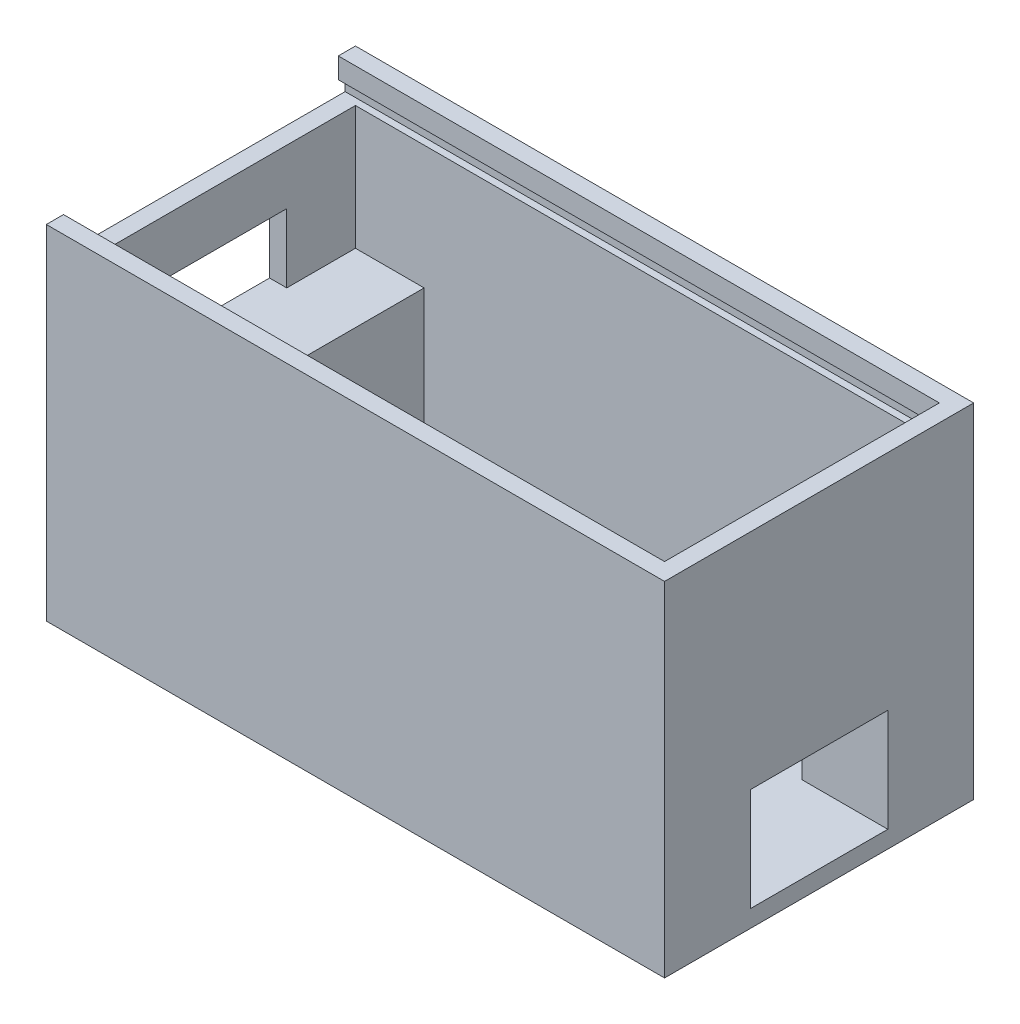
SolidWorks part; units mm, degrees
ref_plane "Front Plane" through (0, 0, 0) normal (0, 0, 1) x (1, 0, 0)
ref_plane "Top Plane" through (0, 0, 0) normal (0, 1, 0) x (1, 0, 0)
ref_plane "Right Plane" through (0, 0, 0) normal (1, 0, 0) x (0, 0, -1)
sketch "Sketch1" plane through (0, 0, 0) normal (0, 1, 0) x (1, 0, 0)
  line L1 (-40.1376, 25.9551) -> (49.8624, 25.9551)
  line L2 (-40.1376, 25.9551) -> (-40.1376, -19.0449)
  line L3 (-40.1376, -19.0449) -> (49.8624, -19.0449)
  line L4 (49.8624, 25.9551) -> (49.8624, -19.0449)
extrude "Boss-Extrude1" add sketch "Sketch1" along normal blind 50
shell "Shell1" thickness 2.5 removed face at (4.8624, 50, -3.4551)
sketch "Sketch2" plane through (-37.6376, 0, 0) normal (1, 0, 0) x (0, 0, -1)
  line L0 (-16.5449, 50) -> (-16.5449, 2.5) construction
  line L1 (23.4551, 2.5) -> (-16.5449, 2.5)
  line L2 (23.4551, 2.5) -> (23.4551, 27)
  line L3 (23.4551, 27) -> (-16.5449, 27)
  line L4 (-16.5449, 2.5) -> (-16.5449, 27)
extrude "Boss-Extrude2" add sketch "Sketch2" along normal blind 10
sketch "Sketch3" plane through (47.3624, 0, 0) normal (-1, 0, 0) x (0, 0, 1)
  line L0 (16.5449, 50) -> (16.5449, 2.5) construction
  line L5 (-23.4551, 2.5) -> (16.5449, 2.5)
  line L6 (-23.4551, 2.5) -> (-23.4551, 22)
  line L7 (-23.4551, 22) -> (16.5449, 22)
  line L8 (16.5449, 2.5) -> (16.5449, 22)
extrude "Boss-Extrude3" add sketch "Sketch3" along normal blind 10
sketch "Sketch9" plane through (-37.6376, 0, 0) normal (1, 0, 0) x (0, 0, -1)
  line L1 (23.4551, 27) -> (-16.5449, 27) construction
  line L2 (13.4551, 37) -> (-6.5449, 37)
  line L3 (13.4551, 37) -> (13.4551, 27)
  line L4 (13.4551, 27) -> (-6.5449, 27)
  line L5 (-6.5449, 37) -> (-6.5449, 27)
  line L6 (13.4551, 37) -> (-6.5449, 27) construction
  line L7 (13.4551, 27) -> (-6.5449, 37) construction
  point P3 (3.4551, 34.5)
  point P4 (3.4551, 32)
extrude "Cut-Extrude3" cut sketch "Sketch9" against normal blind 2.5
sketch "Sketch11" plane through (37.3624, 0, 0) normal (-1, 0, 0) x (0, 0, 1)
  line L0 (-23.4551, 2.5) -> (16.5449, 2.5) construction
  line L4 (-13.4551, 17.5) -> (6.5449, 17.5)
  line L5 (-13.4551, 17.5) -> (-13.4551, 2.5)
  line L6 (-13.4551, 2.5) -> (6.5449, 2.5)
  line L7 (6.5449, 17.5) -> (6.5449, 2.5)
  line L8 (-13.4551, 17.5) -> (6.5449, 2.5) construction
  line L9 (-13.4551, 2.5) -> (6.5449, 17.5) construction
  point P6 (-3.4551, 10)
extrude "Cut-Extrude5" cut sketch "Sketch11" against normal blind 12.5
sketch "Sketch13" plane through (-37.6376, 0, 0) normal (1, 0, 0) x (0, 0, -1)
  line L0 (-16.5449, 50) -> (-16.5449, 27) construction
  line L1 (23.4551, 50) -> (-16.5449, 50)
  line L2 (23.4551, 50) -> (23.4551, 45)
  line L3 (23.4551, 45) -> (-16.5449, 45)
  line L4 (-16.5449, 50) -> (-16.5449, 45)
extrude "Cut-Extrude6" cut sketch "Sketch13" against normal blind 2.5
sketch "Sketch14" plane through (0, 0, -23.4551) normal (0, 0, 1) x (1, 0, 0)
  line L0 (47.3624, 50) -> (47.3624, 22) construction
  line L1 (-40.1376, 45) -> (47.3624, 45)
  line L2 (-40.1376, 45) -> (-40.1376, 47)
  line L3 (-40.1376, 47) -> (47.3624, 47)
  line L4 (47.3624, 45) -> (47.3624, 47)
sketch "Sketch15" plane through (0, 0, 16.5449) normal (0, 0, -1) x (-1, 0, 0)
  line L0 (-47.3624, 50) -> (-47.3624, 22) construction
  line L1 (40.1376, 45) -> (-47.3624, 45)
  line L2 (40.1376, 45) -> (40.1376, 47)
  line L3 (40.1376, 47) -> (-47.3624, 47)
  line L4 (-47.3624, 45) -> (-47.3624, 47)
extrude "Cut-Extrude7" cut sketch "Sketch14" against normal blind 1
extrude "Cut-Extrude8" cut sketch "Sketch15" against normal blind 1
